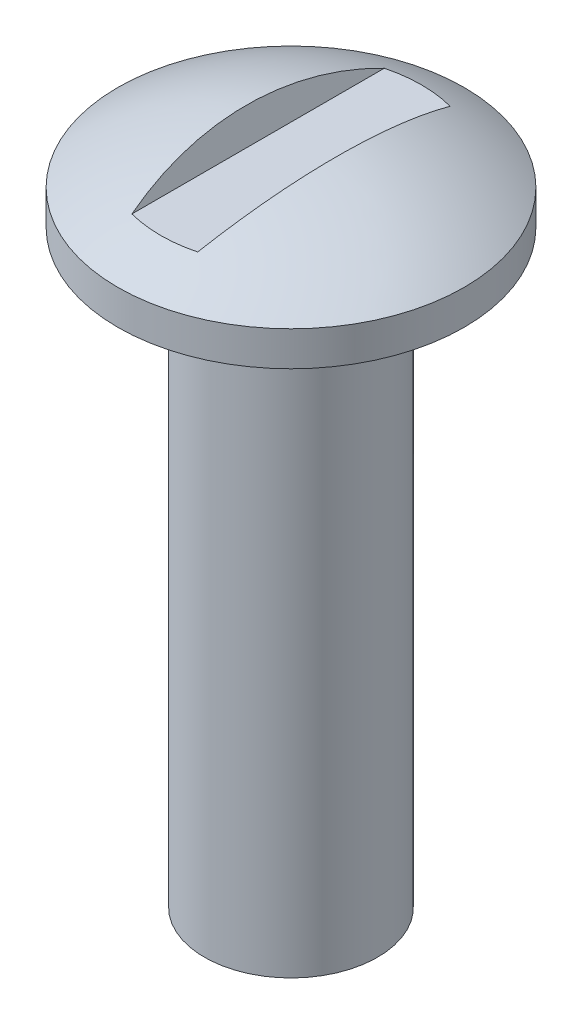
SolidWorks part; units mm, degrees
ref_plane "Front Plane" through (0, 0, 0) normal (0, 0, 1) x (1, 0, 0)
ref_plane "Top Plane" through (0, 0, 0) normal (0, 1, 0) x (1, 0, 0)
ref_plane "Right Plane" through (0, 0, 0) normal (1, 0, 0) x (0, 0, -1)
sketch "Sketch1" plane through (0, 0, 0) normal (0, 0, 1) x (1, 0, 0)
  line L0 (0, 0) -> (0, 82.1313) construction
  line L1 (0, 0) -> (0, 45.72)
  line L2 (0, 45.72) -> (-12.7, 45.72)
  line L3 (-12.7, 45.72) -> (-12.7, 43.18)
  line L4 (-12.7, 43.18) -> (-6.35, 43.18)
  line L5 (-6.35, 43.18) -> (-6.35, 0)
  line L6 (-6.35, 0) -> (-0.4532, 0)
  line L7 (0, 0) -> (-0.4532, 0)
  dimension "D1" = 43.18
  dimension "D2" = 2.54
  dimension "D3" = 25.4
  dimension "D4" = 12.7
revolve "Revolve2" add sketch "Sketch1" angle 360 about L0
dome "Dome1" faces to dome 1 distance 3.81 reverse direction no elliptical dome no face at (0, 45.72, -12.7) parameters "D1"=3.81
sketch "Sketch2" plane through (0, 0, 0) normal (0, 0, 1) x (1, 0, 0)
  line L0 (0, 0) -> (0, 67.5328) construction
  line L1 (7.0999, 57.307) -> (-7.0999, 57.307)
  line L2 (-7.0999, 57.307) -> (-2.4131, 47.454)
  line L3 (-2.4131, 47.454) -> (2.4131, 47.454)
  line L4 (7.0999, 57.307) -> (2.4131, 47.454)
  point P8 (0, 47.454)
  point P9 (0, 57.307)
extrude "Cut-Extrude1" cut sketch "Sketch2" against normal through all both and the other way through all
